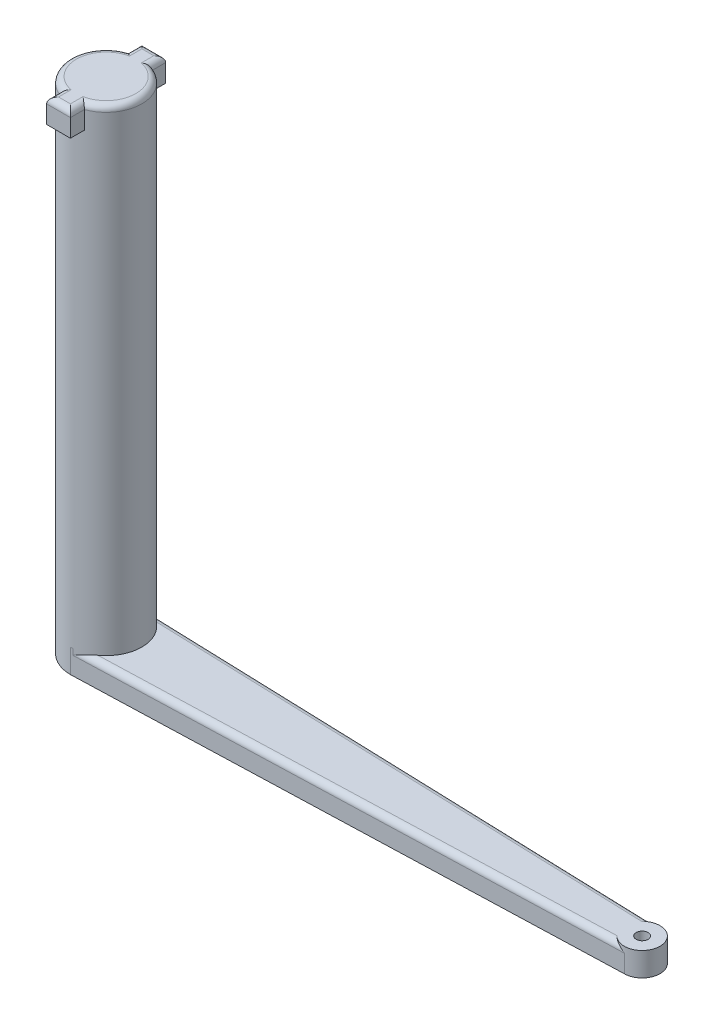
SolidWorks part; units mm, degrees
ref_plane "Front Plane" through (0, 0, 0) normal (0, 0, 1) x (1, 0, 0)
ref_plane "Top Plane" through (0, 0, 0) normal (0, 1, 0) x (1, 0, 0)
ref_plane "Right Plane" through (0, 0, 0) normal (1, 0, 0) x (0, 0, -1)
sketch "Sketch1" plane through (0, 0, 0) normal (0, 1, 0) x (1, 0, 0)
  circle A0 centre (0, 0) radius 30
extrude "Boss-Extrude1" add sketch "Sketch1" along normal blind 400
sketch "Sketch2" plane through (0, 400, 0) normal (0, 1, 0) x (1, 0, 0)
  line L1 (-10, -40) -> (10, -40)
  line L2 (-10, -40) -> (-10, 40)
  line L3 (-10, 40) -> (10, 40)
  line L4 (10, -40) -> (10, 40)
  line L5 (-10, -40) -> (10, 40) construction
  line L6 (-10, 40) -> (10, -40) construction
  point P0 (0, 0)
extrude "Boss-Extrude2" add sketch "Sketch2" against normal blind 20
fillet "Fillet2" radius 5 8 edges at (-10, 400, -34.1421) (0, 400, -40) (10, 400, -34.1421) (30, 400, 0) (10, 400, 34.1421) (0, 400, 40) (-10, 400, 34.1421) (-30, 400, 0)
sketch "Sketch3" plane through (0, 0, 0) normal (0, -1, 0) x (1, 0, 0)
  line L1 (450, -15) -> (0, -30)
  line L2 (450, 15) -> (0, 30)
  circle A2 centre (450, 0) radius 15
  arc A3 (-10, -28.2843) -> (10, -28.2843) centre (0, 0) ccw construction
  arc A4 (0, -30) -> (0, 30) centre (0, 0) cw
  circle M4 centre (0, 0) radius 30
extrude "Boss-Extrude3" add sketch "Sketch3" along normal blind 20 contours A2 L2 L1 M4 | A2 | L2 L1 M4 region at (209.6645, 0, 0) region at (450, 0, 0) region at (0, 0, 0)
fillet "Fillet3" radius 5 2 edges at (0, -10, 30) (0, -10, -30)
fillet "Fillet7" radius 5 2 edges at (225.9989, 0, 22.4667) (225.9989, 0, -22.4667)
sketch "Sketch4" plane through (0, 0, 0) normal (0, 1, 0) x (1, 0, 0)
  circle A0 centre (450, 0) radius 5
extrude "Cut-Extrude1" cut sketch "Sketch4" against normal blind 20
